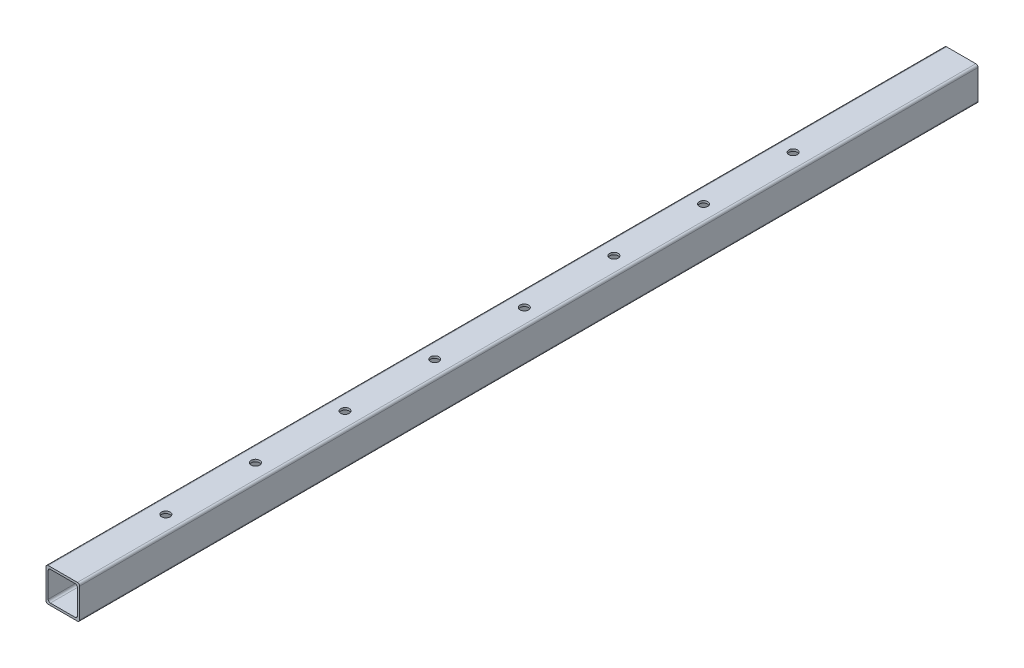
SolidWorks part; units mm, degrees
ref_plane "Front Plane" through (0, 0, 0) normal (0, 0, 1) x (1, 0, 0)
ref_plane "Top Plane" through (0, 0, 0) normal (0, 1, 0) x (1, 0, 0)
ref_plane "Right Plane" through (0, 0, 0) normal (1, 0, 0) x (0, 0, -1)
sketch "Sketch1" plane through (0, 0, 0) normal (0, 0, 1) x (1, 0, 0)
  line L0 (-9.525, 0) -> (9.525, 0) construction
  line L1 (0, -9.525) -> (0, 9.525) construction
  line L2 (8.2804, 0) -> (8.2804, 8.2804) construction
  line L3 (-9.525, -9.525) -> (9.525, -9.525) construction
  line L4 (-9.525, -9.525) -> (-9.525, 9.525) construction
  line L5 (-9.525, 9.525) -> (9.525, 9.525) construction
  line L6 (9.525, -9.525) -> (9.525, 9.525) construction
  line L7 (-9.525, -9.525) -> (9.525, 9.525) construction
  line L8 (-9.525, 9.525) -> (9.525, -9.525) construction
  line L9 (8.2804, 8.2804) -> (-8.2804, 8.2804) construction
  line L10 (-8.2804, 8.2804) -> (-8.2804, -8.2804) construction
  line L11 (-8.2804, -8.2804) -> (8.2804, -8.2804) construction
  line L12 (8.2804, -8.2804) -> (8.2804, 0) construction
  point P0 (0, 0)
  point P4 (0, 0)
  point P9 (0, 0)
  point P10 (8.2804, 0)
  point P13 (0, -8.2804)
  point P14 (-8.2804, 0)
  point P15 (0, 8.2804)
  dimension "Width" = 19.05
  dimension "Wall Thickness" = 1.2446
  dimension "Height" = 19.05
  dimension "D1" = 1.2446
  dimension "D2" = 1.2446
  dimension "D3" = 1.2446
sketch "Sketch2" plane through (0, 0, 0) normal (1, 0, 0) x (0, 0, -1)
  line L0 (254.635, 9.525) -> (-254.635, 9.525) construction
  point P3 (-232.7275, 9.525)
  point P5 (232.7275, 9.525)
  point P7 (0, 9.525)
  dimension "D1" = 21.9075
  dimension "D2" = 21.9075
  dimension "Length" = 509.27
sketch "Sketch3" plane through (0, 0, 0) normal (0, 0, 1) x (1, 0, 0)
  line L1 (9.525, 9.525) -> (-9.525, 9.525)
  line L2 (-9.525, 9.525) -> (-9.525, -9.525)
  line L3 (-9.525, -9.525) -> (9.525, -9.525) construction
  line L4 (-9.525, -9.525) -> (9.525, -9.525)
  line L5 (9.525, -9.525) -> (9.525, 9.525)
  line L6 (-8.2804, 8.2804) -> (8.2804, 8.2804)
  line L7 (8.2804, 8.2804) -> (8.2804, -8.2804)
  line L8 (8.2804, -8.2804) -> (-8.2804, -8.2804)
  line L9 (-8.2804, -8.2804) -> (-8.2804, 8.2804)
extrude "Boss-Extrude1" add sketch "Sketch3" along normal mid plane 509.27
fillet "Fillet1" radius 1.2446 8 edges at (-9.525, 9.525, 0) (8.2804, -8.2804, 0) (-8.2804, -8.2804, 0) (-8.2804, 8.2804, 0) (8.2804, 8.2804, 0) (9.525, -9.525, 0) (-9.525, -9.525, 0) (9.525, 9.525, 0)
sketch "Sketch4" plane through (0, 9.525, 0) normal (0, 1, 0) x (1, 0, 0)
  line L0 (0, 254.635) -> (0, 159.385) construction
  line L1 (8.2804, 254.635) -> (-8.2804, 254.635) construction
  line L2 (0, 159.385) -> (0, 108.585) construction
  circle A0 centre (0, 159.385) radius 2.413
  circle A1 centre (0, 108.585) radius 2.413
  circle A2 centre (0, 57.785) radius 2.413
  circle A3 centre (0, 6.985) radius 2.413
  circle A4 centre (0, -43.815) radius 2.413
  circle A5 centre (0, -94.615) radius 2.413
  circle A6 centre (0, -145.415) radius 2.413
  circle A7 centre (0, -196.215) radius 2.413
  dimension "D2" = 4.826
  dimension "D4" = 4.826
  dimension "D1" = 95.25
  dimension "D3" = 50.8
  dimension "D5" = 7
extrude "Cut-Extrude1" cut sketch "Sketch4" against normal up to next
sketch "Sketch6" plane through (-9.525, 0, 0) normal (-1, 0, 0) x (0, 0, 1)
  line L0 (-254.635, 0) -> (-179.705, 0) construction
  line L1 (-254.635, 8.2804) -> (-254.635, -8.2804) construction
  line L2 (-182.118, -1.651) -> (-187.198, -1.651)
  line L7 (-182.118, -6.477) -> (-177.292, -1.651) construction
  line L12 (-177.292, -6.477) -> (-182.118, -6.477)
  line L13 (-177.292, -6.477) -> (-177.292, -1.651)
  line L14 (-177.292, -1.651) -> (-182.118, -1.651)
  line L15 (-182.118, -6.477) -> (-182.118, -1.651) construction
  line L16 (-192.278, 9.525) -> (-192.278, -6.477)
  line L17 (-177.292, -6.477) -> (-182.118, -1.651) construction
  line L18 (-254.635, 9.525) -> (254.635, 9.525) construction
  line L19 (-192.278, -6.477) -> (-182.118, -6.477)
  line L20 (-187.198, -1.651) -> (-187.198, 9.525)
  line L21 (-187.198, 9.525) -> (-192.278, 9.525)
  point P12 (-179.705, -4.064)
  dimension "D1" = 74.93
  dimension "D2" = 16.002
  dimension "D3" = 4.826
  dimension "D4" = 4.826
  dimension "D5" = 10.16
  dimension "D6" = 5.08
extrude "Cut-Extrude3" [suppressed] cut sketch "Sketch6" along normal blind 6.35 from surface
pattern_linear "LPattern2" [suppressed] count 8 spacing 50.8 of bodies 108
equation "\"D1@Boss-Extrude1\" = \"Length@Sketch2\""
equation "\"D1@Sketch2\" = \"Width@Sketch1\" * 1.15"
equation "\"D2@Sketch2\"=\"D1@Sketch2\""
equation "\"D1@Sketch1\"=\"Wall Thickness@Sketch1\""
equation "\"D2@Sketch1\"=\"Wall Thickness@Sketch1\""
equation "\"D3@Sketch1\"=\"Wall Thickness@Sketch1\""
equation "\"D1@Fillet1\"=\"Wall Thickness@Sketch1\""
